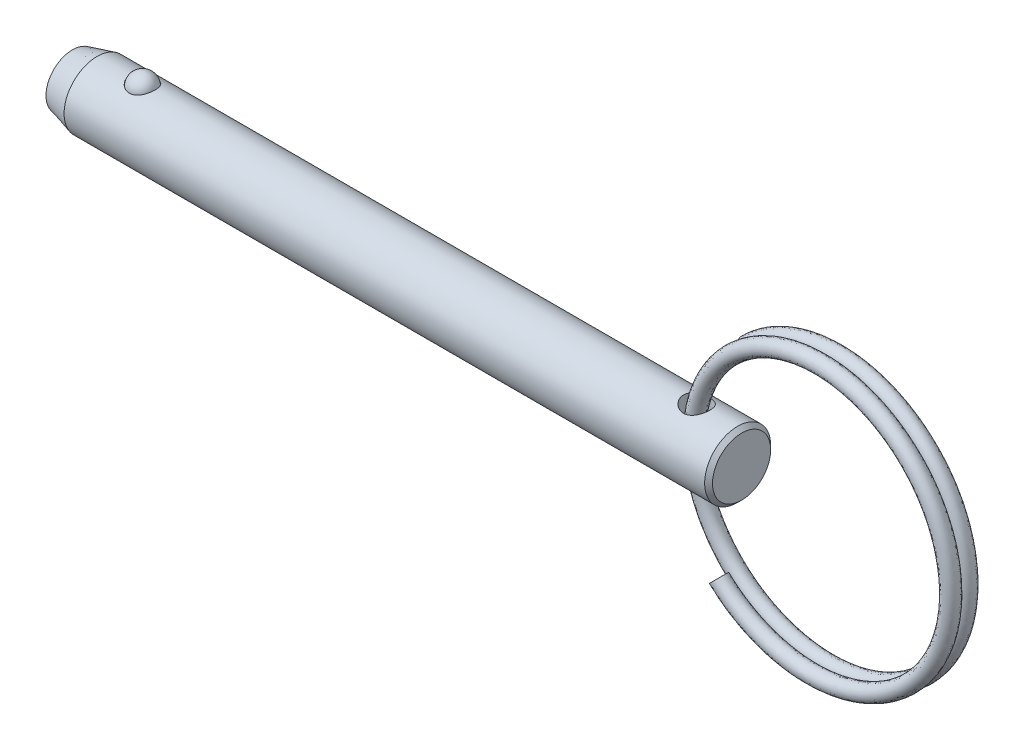
SolidWorks part; units mm, degrees
ref_plane "Front" through (0, 0, 0) normal (0, 0, 1) x (1, 0, 0)
ref_plane "Top" through (0, 0, 0) normal (0, 1, 0) x (1, 0, 0)
ref_plane "Right" through (0, 0, 0) normal (1, 0, 0) x (0, 0, -1)
sketch "Sketch1" plane through (0, 0, 0) normal (0, 0, 1) x (1, 0, 0)
  line L0 (32.1564, 2.794) -> (31.7754, 3.175)
  line L1 (31.7754, 3.175) -> (32.1564, 3.175) construction
  line L4 (32.1564, 2.794) -> (32.1564, 0)
  line L5 (32.1564, 3.175) -> (32.1564, 2.794) construction
  line L16 (31.7754, 3.175) -> (-29.7865, 3.175)
  line L17 (-32.1564, 3.175) -> (-32.1564, 2.54) construction
  line L19 (-29.7865, 3.175) -> (-32.1564, 3.175) construction
  line L22 (-32.1564, -3.175) -> (-29.7865, -3.175) construction
  line L23 (-25.4219, 2.8575) -> (-25.4219, -2.8575) construction
  line L24 (-32.1564, 0) -> (32.1564, 0)
  line L27 (32.1564, 0) -> (34.9504, 0) construction
  line L29 (-32.1564, 0) -> (-32.1564, -2.54) construction
  line L36 (26.5684, 0) -> (26.5684, 3.175) construction
  line L37 (-32.1564, 2.54) -> (-32.1564, 0)
  line L38 (-29.7865, -3.175) -> (32.1564, -3.175) construction
  line L39 (-32.1564, -2.54) -> (-32.1564, -3.175) construction
  line L40 (-29.7865, 3.175) -> (-32.1564, 2.54)
  line L42 (-29.7865, -3.175) -> (-32.1564, -2.54) construction
  line L43 (-29.7865, 3.175) -> (-29.7865, -3.175) construction
  circle A2 centre (-25.4219, 2.8575) radius 1.2319 construction
  point P35 (-24.2316, 3.175)
  dimension "D2" = 5.715
  dimension "D11" = 0.9144
  dimension "A" = 6.35
  dimension "D" = 5.588
  dimension "E" = 7.2644
  dimension "D3" = 0.381
  dimension "Useable Length" = 50.8
  dimension "D12" = 5.08
  dimension "C" = 7.9248
  dimension "A1" = 15
revolve "Revolve1" add sketch "Sketch1" angle 360 about L27
sketch "Sketch2" plane through (0, 0, 0) normal (0, 0, 1) x (1, 0, 0)
  line L0 (-24.1646, 2.8575) -> (-26.6792, 2.8575)
  line L1 (-25.4219, 4.0894) -> (-25.4219, 4.1148) construction
  line L2 (-24.1646, 2.8575) -> (-21.65, 2.8575) construction
  circle A0 centre (-25.4219, 2.8575) radius 1.2319 construction
  circle A1 centre (-25.4219, 2.8575) radius 1.2319 construction
  arc A2 (-26.6792, 2.8575) -> (-24.1646, 2.8575) centre (-25.4219, 2.8575) cw
  dimension "D1" = 0.0254
revolve "Cut-Revolve1" cut sketch "Sketch2" angle 360 about L2
sketch "Sketch3" plane through (0, 0, 0) normal (0, 0, 1) x (1, 0, 0)
  line L0 (-24.19, 2.8575) -> (-26.6538, 2.8575)
  line L1 (-24.19, 2.8575) -> (-21.7262, 2.8575) construction
  circle A0 centre (-25.4219, 2.8575) radius 1.2319 construction
  arc A1 (-24.19, 2.8575) -> (-26.6538, 2.8575) centre (-25.4219, 2.8575) ccw
revolve "Revolve2" add sketch "Sketch3" angle 360 about L1
sketch "Sketch4" plane through (0, 0, 0) normal (0, 0, 1) x (1, 0, 0)
  line L1 (27.8384, -3.175) -> (29.1084, -3.175)
  line L2 (27.8384, -3.175) -> (27.8384, 3.175)
  line L3 (27.8384, 3.175) -> (29.1084, 3.175)
  line L4 (29.1084, -3.175) -> (29.1084, 3.175)
  line L5 (27.8384, -3.175) -> (27.8384, -4.445) construction
  line L6 (29.1084, 3.175) -> (32.1564, 3.175) construction
  line L8 (26.5684, -3.175) -> (26.5684, 3.175) construction
  line L9 (26.5684, 0) -> (27.8384, 0) construction
  line L11 (27.8384, 0) -> (29.1084, 0) construction
  line L12 (31.7754, 3.175) -> (-29.7865, 3.175) construction
  line L14 (-29.7865, -3.175) -> (32.1564, -3.175) construction
  dimension "D1" = 2.54
revolve "Cut-Revolve2" cut sketch "Sketch4" angle 360 about L2
sketch "Sketch5" plane through (0, 0, 0) normal (0, 0, 1) x (1, 0, 0)
  line L0 (0, 0) -> (26.8614, 0) construction
  line L1 (26.8614, 0) -> (26.8614, 3.175) construction
  line L2 (31.7754, 3.175) -> (-29.7865, 3.175) construction
  line L3 (40.3234, 0) -> (53.7854, 0) construction
  line L4 (29.1084, 3.175) -> (28.8154, 3.175) construction
  line L5 (27.8384, 3.175) -> (29.1084, 3.175) construction
  line L6 (27.2412, 3.175) -> (27.2412, -3.175) construction
  line L7 (26.8614, 3.175) -> (26.5684, 3.175) construction
  line L8 (27.8384, -3.175) -> (29.1084, -3.175) construction
  line L9 (27.2412, -3.175) -> (29.1084, -3.175) construction
  line L10 (26.8614, 0) -> (40.3234, 0) construction
  line L12 (28.8154, 3.175) -> (27.2412, 3.175) construction
  line L13 (40.3234, 11.938) -> (40.3234, 13.462) construction
  circle A0 centre (40.3234, 0) radius 13.462
  circle A1 centre (40.3234, 0) radius 11.938 construction
  circle A2 centre (40.3234, 0) radius 12.7 construction
  point P26 (40.3234, 12.7)
  dimension "R Ring Dia" = 25.4
  dimension "Ring OD" = 1.524
curve "Helix/Spiral1" pitch 1.5494 height 1.3557 radius 13.462 left hand yes centre (40.3234, 0, 0) axis (0, 0, -1) start towards (1, 0, 0)
sketch "Sketch6" plane through (114.0038, 0, 0) normal (0, 1, 0) x (0, 0, -1)
  line L0 (0, 85.6184) -> (0, 86.3804) construction
  line L1 (0, 86.3804) -> (0, 87.1424) construction
  circle A0 centre (0, 86.3804) radius 0.762
  dimension "D1" = 1.524
sketch "Sketch7" plane through (0, 0, 0) normal (0, 0, 1) x (1, 0, 0)
  circle A0 centre (40.3234, 0) radius 13.462 construction
  circle A1 centre (40.3234, 0) radius 13.462
curve "Helix/Spiral2" pitch 1.5494 height 1.3557 radius 13.462 left hand yes centre (40.3234, 0, 0) axis (0, 0, 1) start towards (1, 0, 0)
sweep "Sweep1" add profiles "Sketch6" path "Helix/Spiral1"
sweep "Sweep2" add profiles "Sketch6<2>" path "Helix/Spiral2"
sketch "Sketch6<2>" plane through (114.0038, 0, 0) normal (0, 1, 0) x (0, 0, -1) same geometry as "Sketch6"
equation "\"D12@Sketch1\"=\"A@Sketch1\" * 0.80"
equation "\"D2@Sketch1\"=\"A@Sketch1\" * 0.9"
equation "\"D1@Sketch4\" = \"A@Sketch1\" / 2.5"
equation "\"Ring OD@Sketch5\" = \"R Ring Dia@Sketch5\" * 0.06"
equation "\"D4@Helix/Spiral1\"=\"Ring OD@Sketch5\" + 0.001"
equation "\"D1@Sketch6\"=\"Ring OD@Sketch5\""
equation "\"D4@Helix/Spiral2\" = \"D4@Helix/Spiral1\""
equation "\"D5@Helix/Spiral2\" = \"D5@Helix/Spiral1\""
